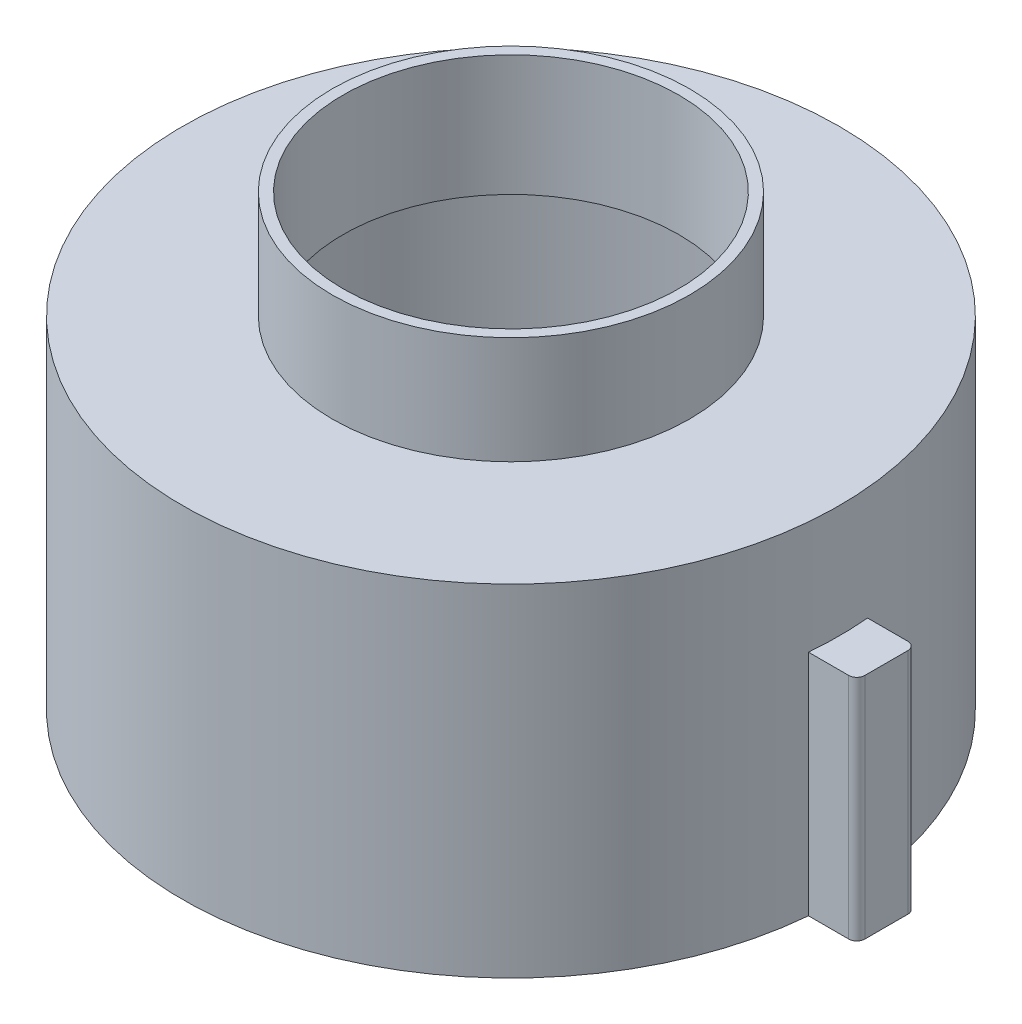
SolidWorks part; units mm, degrees
other "DetailItem1"
other "Weld Folder"
other "Weld Bead1"
ref_plane "Front Plane" through (0, 0, 0) normal (0, 0, 1) x (1, 0, 0)
ref_plane "Top Plane" through (0, 0, 0) normal (0, 1, 0) x (1, 0, 0)
ref_plane "Right Plane" through (0, 0, 0) normal (1, 0, 0) x (0, 0, -1)
sketch "Sketch1" plane through (0, 0, 0) normal (0, 0, 1) x (1, 0, 0)
  line L0 (-122.25, -5) -> (-118.25, -5)
  line L1 (-118.25, -5) -> (-118.25, 2)
  line L2 (-118.25, 2) -> (-115.25, 2)
  line L7 (-115.25, 2) -> (-115.25, 117)
  line L8 (-115.25, 122) -> (-122.25, 122)
  line L9 (-122.25, 122) -> (-122.25, -5)
  line L10 (0, 0) -> (0, 131.3181) construction
  line L11 (-115.25, 122) -> (-66.5, 122)
  line L12 (-66.5, 122) -> (-66.5, 162)
  line L13 (-62.5, 162) -> (-62.5, 117)
  line L14 (-62.5, 117) -> (-115.25, 117)
  line L15 (-62.5, 162) -> (-66.5, 162)
  dimension "D1" = 244.5
  dimension "D3" = 4
  dimension "D4" = 7
  dimension "D6" = 2
  dimension "D5" = 120
  dimension "D2" = 7
  dimension "D7" = 4
  dimension "D8" = 133
  dimension "D9" = 5
  dimension "D10" = 40
revolve "Revolve1" add sketch "Sketch1" angle 360 about L10
sketch "Sketch3" plane through (0, 0, 0) normal (1, 0, 0) x (0, 0, -1)
  line L0 (0, -5) -> (0, 65) construction
  line L1 (-9.5, -5) -> (-9.5, 65)
  line L2 (9.5, -5) -> (9.5, 65)
  line L3 (-122.25, -5) -> (122.25, -5) construction
  arc A0 (-9.5, -5) -> (9.5, -5) centre (0, -5) ccw
  arc A1 (9.5, 65) -> (-9.5, 65) centre (0, 65) ccw
  point P3 (0, 30)
  dimension "D1" = 19
  dimension "D2" = 70
extrude "Cut-Extrude1" cut sketch "Sketch3" against normal through all both and the other way through all
sketch "Sketch2" plane through (0, 0, 0) normal (0, 1, 0) x (1, 0, 0)
  line L0 (139.7373, -11) -> (138.2373, -9.5) construction
  line L1 (117.7373, 11) -> (139.7373, 11)
  line L2 (117.7373, 11) -> (117.7373, -11)
  line L3 (117.7373, -11) -> (139.7373, -11)
  line L4 (139.7373, 11) -> (139.7373, -11)
  line L5 (138.2373, -9.5) -> (114.8578, -9.5)
  line L6 (138.2373, -9.5) -> (138.2373, 9.5)
  line L7 (138.2373, 9.5) -> (114.8578, 9.5)
  line L8 (114.8578, -9.5) -> (114.8578, 9.5)
  line L9 (138.2373, 9.5) -> (139.7373, 11) construction
  circle A0 centre (0, 0) radius 118.25 construction
  circle A1 centre (0, 0) radius 115.25 construction
  point P4 (117.7373, 0)
  dimension "D1" = 22
  dimension "D2" = 1.5
  dimension "D3" = 1.5
extrude "Boss-Extrude2" add sketch "Sketch2" along normal blind 85 from offset 5 contours L7 L6 L5 L2 L3 L4 L1 region at (128.7373, 0, -10.6889) offset against normal yes
sketch "Sketch5" plane through (0, 80, 0) normal (0, 1, 0) x (1, 0, 0)
  line L0 (138.2373, 9.5) -> (121.8803, 9.5) construction
  line L1 (138.2373, -9.5) -> (138.2373, 9.5) construction
  line L2 (138.2373, -9.5) -> (121.8803, -9.5) construction
  line L3 (138.2373, 9.5) -> (121.8803, 9.5)
  line L4 (138.2373, -9.5) -> (138.2373, 9.5)
  line L5 (138.2373, -9.5) -> (121.8803, -9.5)
  circle A0 centre (0, 0) radius 122.25 construction
  circle A1 centre (0, 0) radius 122.25
  line M6 (121.8803, 9.5) -> (138.2373, 9.5)
  line M7 (138.2373, 9.5) -> (138.2373, -9.5)
  line M8 (138.2373, -9.5) -> (121.8803, -9.5)
extrude "Boss-Extrude3" add sketch "Sketch5" against normal blind 3 contours A1 M8 M7 M6 region at (130.1817, 80, 0)
fillet "Fillet1" radius 1.5 2 edges at (138.2373, 36, -9.5) (138.2373, 36, 9.5)
fillet "Fillet2" radius 3 2 edges at (139.7373, 37.5, -11) (139.7373, 37.5, 11)
mirror "Mirror1" about plane through (0, 0, 0) normal (1, 0, 0) of "Boss-Extrude2", "Boss-Extrude3", "Fillet1", "Fillet2"
equation "\"d_ext_rouleau\"= 90"
equation "\"epaisseur_rouleau\"=80"
equation "\"alesage-rouleau\"= 52"
equation "\"jeu_dent_rouleau\"= 2"
equation "\"profondeur_dent_rouleau\"=4"
equation "\"n_dent_roueau\"= 15"
equation "\"d_ext_roulement_rouleau\"= 42"
equation "\"d_int_roulement_rouleau\"= 20"
equation "\"B_roulement_rouleau\"= 12"
equation "\"r_roulement_rouleau\"= 0.6"
equation "\"d_bille_roulement_rouleau\"= 8"
equation "\"F_anneau_alesage_rouleau\"=1.85"
equation "\"G_anneau_alesage_rouleau\"=47.5"
equation "\"K_anneau_alesage_rouleau\"=3.75"
equation "\"d_vis_flasque_rouleau\"=5"
equation "\"l-x_vis_flasque_rouleau\"=4"
equation "\"g_anneau_arbre_rouleau\"=19"
equation "\"f_anneau_arbre_rouleau\"=1.3"
equation "\"k_anneau_arbre_rouleau\"=1.5"
equation "\"entrax_vis_rouleau\"=65"
equation "\"d_granulat\"= 8"
equation "\"h_matrice\"= 18"
equation "\"d_matrice\"= 220"
equation "\"zone_vide_matrice\" = 48"
equation "\"d_alesage_matrice\"=20"
equation "\"a_clavette_alesage_matrice\"=6"
equation "\"B_roulement_matrice\"= 12"
equation "\"d_ext_roulement_matrice\"= 42"
equation "\"d_int_roulement_matrice\"= 20"
equation "\"r_roulement_matrice\"= 1"
equation "\"h_epaulement_arbre_matrice\" = 100"
equation "\"j_clavette_arbre_matrice\" = 6"
equation "\"g_anneaux_arbre_matrice\" = 16.2"
equation "\"f_anneaux_arbre_matrice\" = 1.1"
equation "\"B_roulement_bc_arbre_matrice\"= 10"
equation "\"e_anneaux_arbre_matrice\" = 1"
equation "\"h_polie_matrice\" = 40"
equation "\"l_arbre_matrice\" = 300"
equation "\"d_int_ecrou_encouch_matrice\" = 20"
equation "\"d_ext_ecrou_encouch_matrice\" = 32"
equation "\"b_ecrou_encouch_matrice\" = 6"
equation "\"s_ecrou_encouch_matrice\" = 4"
equation "\"G_ecrou_encouch_matrice\" = 1"
equation "\"E_ecrou_encouch_matrice\" = 4"
equation "\"d_int_roulement_conique_matrice\"=25"
equation "\"d_ext_roulement_conique_matrice\"=52"
equation "\"b_roulement_conique_matrice\"=16.25"
equation "\"d_int_roulement_bc_matrice\"=20"
equation "\"d_ext_roulement_bc_matrice\"=42"
equation "\"b_roulement_bc_matrice\"=12"
equation "\"d_tube_sup_carter\"=244.5"
equation "\"e_tube_sup_carter\"=12"
equation "\"d_tube_inf_catrer\"= 168.3"
equation "\"e_tube_inf_carter\"= 6"
equation "\"D1@Sketch1\" = \"d_tube_inf_carter_cache\""
equation "\"D5@Sketch1\"=\"d_ext_rouleau\"+30"
equation "\"d_tube_inf_carter_cache\" = 244.5"
equation "\"e_tube_inf_carter_cache\" = 8"
equation "\"D2@Sketch1\"=\"e_tube_inf_carter_cache\"-1"
equation "\"e_tube_sup_carter_cache\" = 4"
equation "\"D7@Sketch1\"=\"e_tube_sup_carter_cache\""
equation "\"d_tube_sup_carter_cache\" = 133"
equation "\"D8@Sketch1\"=\"d_tube_sup_carter_cache\""
equation "\"h_tube_trimee\" = 40"
equation "\"D10@Sketch1\"=\"h_tube_trimee\""
equation "\"D2@Sketch3\"=\"d_ext_rouleau\"-20"
